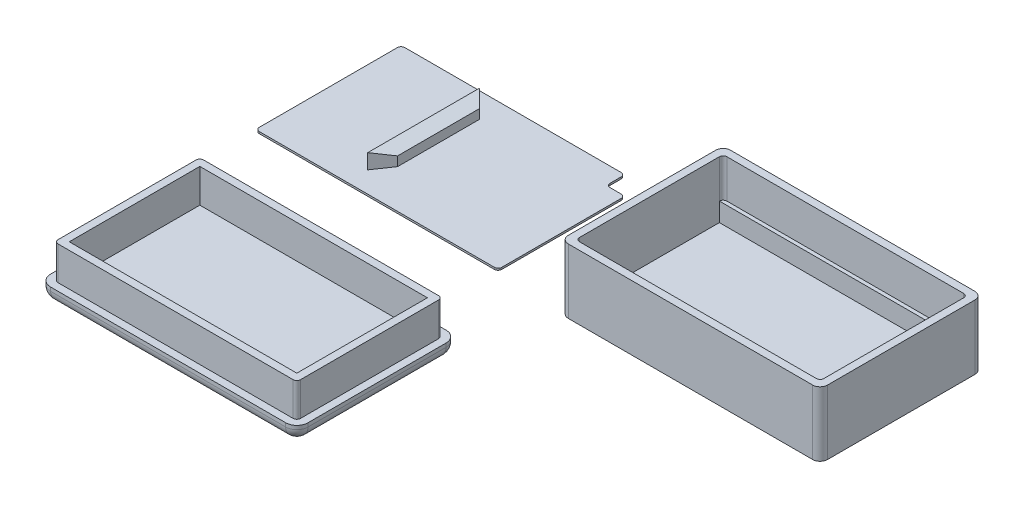
SolidWorks part; units mm, degrees
ref_plane "Front Plane" through (0, 0, 0) normal (0, 0, 1) x (1, 0, 0)
ref_plane "Top Plane" through (0, 0, 0) normal (0, 1, 0) x (1, 0, 0)
ref_plane "Right Plane" through (0, 0, 0) normal (1, 0, 0) x (0, 0, -1)
sketch "Sketch1" plane through (0, 0, 0) normal (0, 1, 0) x (1, 0, 0)
  line L0 (-58.3709, -20.404) -> (-58.3709, 18.596)
  line L1 (-58.3709, 18.596) -> (1.6291, 18.596)
  line L2 (1.6291, 18.596) -> (1.6291, 13.596)
  line L3 (1.6291, 13.596) -> (6.6291, 13.596)
  line L4 (6.6291, 13.596) -> (6.6291, -20.404)
  line L5 (6.6291, -20.404) -> (-58.3709, -20.404)
  dimension "D1" = 39
  dimension "D2" = 65
  dimension "D3" = 60
  dimension "D4" = 34
extrude "Boss-Extrude1" add sketch "Sketch1" along normal blind 0.5
fillet "Fillet2" radius 1 1 edges at (6.6291, 0.25, 20.404)
fillet "Fillet3" radius 1 3 edges at (1.6291, 0.25, -18.596) (1.6291, 0.25, -13.596) (6.6291, 0.25, -13.596)
fillet "Fillet4" radius 1 1 edges at (-58.3709, 0.25, -18.596)
fillet "Fillet5" radius 1 1 edges at (-58.3709, 0.25, 20.404)
sketch "Sketch3" plane through (0, 0, 0) normal (0, -1, 0) x (1, 0, 0)
  line L0 (92.1671, 19.6286) -> (27.1671, 19.6286) construction
  line L1 (92.4171, 19.8786) -> (26.9171, 19.8786)
  line L2 (92.4171, 19.8786) -> (92.4171, -19.6214)
  line L3 (92.4171, -19.6214) -> (26.9171, -19.6214)
  line L4 (26.9171, 19.8786) -> (26.9171, -19.6214)
  line L5 (27.1671, 19.6286) -> (27.1671, -19.3714) construction
  line L6 (92.1671, -19.3714) -> (27.1671, -19.3714) construction
  line L7 (92.1671, 19.6286) -> (92.1671, -19.3714) construction
  line L8 (94.4171, 21.8786) -> (94.4171, -21.6214)
  line L9 (94.4171, -21.6214) -> (24.9171, -21.6214)
  line L10 (24.9171, 21.8786) -> (24.9171, -21.6214)
  line L11 (94.4171, 21.8786) -> (24.9171, 21.8786)
  dimension "D1" = 65
  dimension "D2" = 39
  dimension "D4" = 2
  dimension "D3" = 0.25
extrude "Boss-Extrude2" add sketch "Sketch3" against normal blind 17.3 separate body
sketch "Sketch5" plane through (0, 0, 0) normal (0, -1, 0) x (1, 0, 0)
  line L5 (24.9171, -21.6214) -> (94.4171, -21.6214)
  line L6 (24.9171, -21.6214) -> (24.9171, 21.8786)
  line L7 (24.9171, 21.8786) -> (94.4171, 21.8786)
  line L8 (94.4171, -21.6214) -> (94.4171, 21.8786)
extrude "Boss-Extrude3" add sketch "Sketch5" against normal blind 2 contours L6 L5 L8 L7
fillet "Fillet6" radius 1 1 edges at (26.9171, 9.65, 19.8786)
fillet "Fillet7" radius 1 1 edges at (26.9171, 9.65, -19.6214)
fillet "Fillet8" radius 1 1 edges at (92.4171, 9.65, -19.6214)
fillet "Fillet9" radius 1 1 edges at (92.4171, 9.65, 19.8786)
sketch "Sketch7" plane through (-22.9055, 0.5, 42.5387) normal (0, 1, 0) x (1, 0, 0)
  line L0 (-36.3598, -30.9223) -> (-36.3598, 8.0777)
  line L1 (-36.3598, 8.0777) -> (23.6402, 8.0777)
  line L4 (28.6402, 3.0777) -> (28.6402, -30.9223)
  line L5 (28.6402, -30.9223) -> (-36.3598, -30.9223)
  line L8 (28.6402, 3.0777) -> (28.6402, 8.0777)
  line L9 (28.6402, 8.0777) -> (23.6402, 8.0777)
  dimension "D1" = 39
  dimension "D2" = 65
  dimension "D3" = 60
  dimension "D4" = 34
extrude "Boss-Extrude5" add sketch "Sketch7" against normal blind 9
fillet "Fillet12" radius 1 2 edges at (5.7348, -4, 73.461) (5.7348, -4, 34.461)
fillet "Fillet13" radius 1 2 edges at (-59.2652, -4, 34.461) (-59.2652, -4, 73.461)
sketch "Sketch8" plane through (0, -8.5, 0) normal (0, -1, 0) x (-1, 0, 0)
  line L8 (58.2652, -32.461) -> (-4.7348, -32.461)
  line L9 (61.2652, -72.461) -> (61.2652, -35.461)
  line L10 (-4.7348, -75.461) -> (58.2652, -75.461)
  line L11 (-7.7348, -35.461) -> (-7.7348, -72.461)
  line L12 (58.2652, -32.461) -> (-4.7348, -32.461)
  line L13 (61.2652, -72.461) -> (61.2652, -35.461)
  line L14 (-4.7348, -75.461) -> (58.2652, -75.461)
  line L15 (-7.7348, -35.461) -> (-7.7348, -72.461)
  arc A8 (61.2652, -35.461) -> (58.2652, -32.461) centre (58.2652, -35.461) ccw
  arc A9 (58.2652, -75.461) -> (61.2652, -72.461) centre (58.2652, -72.461) ccw
  arc A10 (-7.7348, -72.461) -> (-4.7348, -75.461) centre (-4.7348, -72.461) ccw
  arc A11 (-4.7348, -32.461) -> (-7.7348, -35.461) centre (-4.7348, -35.461) ccw
  arc A12 (61.2652, -35.461) -> (58.2652, -32.461) centre (58.2652, -35.461) ccw
  arc A13 (58.2652, -75.461) -> (61.2652, -72.461) centre (58.2652, -72.461) ccw
  arc A14 (-7.7348, -72.461) -> (-4.7348, -75.461) centre (-4.7348, -72.461) ccw
  arc A15 (-4.7348, -32.461) -> (-7.7348, -35.461) centre (-4.7348, -35.461) ccw
  dimension "D1" = 2
extrude "Boss-Extrude6" add sketch "Sketch8" along normal blind 4
sketch "Sketch9" plane through (0, 0.5, 0) normal (0, 1, 0) x (1, 0, 0)
  line L8 (3.7348, -36.461) -> (-57.2652, -36.461)
  line L9 (-57.2652, -36.461) -> (-57.2652, -71.461)
  line L10 (-57.2652, -71.461) -> (3.7348, -71.461)
  line L11 (3.7348, -71.461) -> (3.7348, -36.461)
  line L12 (3.7348, -36.461) -> (-57.2652, -36.461)
  line L13 (-57.2652, -36.461) -> (-57.2652, -71.461)
  line L14 (-57.2652, -71.461) -> (3.7348, -71.461)
  line L15 (3.7348, -71.461) -> (3.7348, -36.461)
  dimension "D1" = 2
extrude "Boss-Extrude7" add sketch "Sketch9" against normal up to surface (9 mm away) separate body up to face at (-26.7652, -8.5, 53.961)
combine bodies "Combine1" operation type subtract main body 106 bodies to subtract 107
fillet "Fillet15" radius 3 8 edges at (-61.2652, -12.5, 53.961) (-60.3866, -12.5, 74.5824) (-26.7652, -12.5, 75.461) (6.8561, -12.5, 74.5824) (7.7348, -12.5, 53.961) (6.8561, -12.5, 33.3397) (-26.7652, -12.5, 32.461) (-60.3866, -12.5, 33.3397)
sketch "Sketch19" plane through (0, 0, 0) normal (0, 0, 1) x (1, 0, 0)
  line L0 (-18.7232, 15.7306) -> (-18.7232, 19.7306)
  line L1 (-18.7232, 19.7306) -> (-14.7232, 19.7306) construction
  line L2 (-18.7232, 19.7306) -> (-14.7232, 18.9806)
  line L3 (-14.7232, 18.9806) -> (-14.7232, 16.4806)
  line L4 (-18.7232, 17.7306) -> (-14.7232, 17.7306) construction
  line L5 (-18.7232, 15.7306) -> (-14.7232, 16.4806)
  dimension "D1" = 2
  dimension "D2" = 4
  dimension "D3" = 2.5
extrude "Boss-Extrude8" add sketch "Sketch19" along normal blind 30 separate body
ref_plane "Plane1" through (0, 19.7306, 0) normal (0, 1, 0) x (-1, 0, 0)
sketch "Sketch20" plane through (0, 19.7306, 0) normal (0, 1, 0) x (-1, 0, 0)
  line L0 (18.7232, 30) -> (14.7232, 30)
  line L1 (14.7232, 30) -> (14.7232, 26)
  line L2 (18.7232, 15) -> (14.7232, 15) construction
  line L3 (14.7232, 30) -> (14.7232, 0) construction
  line L4 (14.7232, 26) -> (18.7232, 30)
  line L5 (18.7232, 30) -> (18.7232, 0) construction
  line L6 (14.7232, 0) -> (14.7232, 4)
  line L7 (18.7232, 0) -> (14.7232, 0)
  line L8 (14.7232, 4) -> (18.7232, 0)
  dimension "D1" = 4
extrude "Boss-Extrude9" add sketch "Sketch20" against normal up to surface (3.25 mm away) separate body up to face at (-16.7232, 16.1056, 15)
combine bodies "Combine2" operation type subtract main body 113 bodies to subtract 114 115
fillet "Fillet16" radius 2 4 edges at (94.4171, 8.65, -21.6214) (24.9171, 8.65, -21.6214) (24.9171, 8.65, 21.8786) (94.4171, 8.65, 21.8786)
sketch "Sketch21" plane through (0, 2, 0) normal (0, 1, 0) x (1, 0, 0)
  line L0 (26.9171, -0.1286) -> (92.4171, -0.1286) construction
  line L1 (27.1671, -18.6286) -> (87.1671, -18.6286) construction
  line L2 (27.1671, -18.6286) -> (27.1671, 18.3714) construction
  line L3 (27.1671, 18.3714) -> (87.1671, 18.3714) construction
  line L4 (87.1671, -18.6286) -> (87.1671, 18.3714) construction
  line L5 (26.9171, -18.8786) -> (26.9171, 18.6214) construction
  line L6 (92.4171, -18.8786) -> (92.4171, 18.6214) construction
  line L7 (26.9171, -18.8786) -> (26.9171, 18.6214)
  line L8 (26.9171, 18.6214) -> (87.4171, 18.6214)
  line L9 (87.4171, -18.8786) -> (87.4171, 18.6214)
  line L10 (26.9171, -18.8786) -> (87.4171, -18.8786)
  line L11 (27.9171, -19.8786) -> (91.4171, -19.8786)
  line L12 (92.4171, -18.8786) -> (92.4171, 18.6214)
  line L13 (91.4171, 19.6214) -> (27.9171, 19.6214)
  line L14 (26.9171, 18.6214) -> (26.9171, -18.8786)
  line L15 (27.9171, -19.8786) -> (91.4171, -19.8786)
  line L16 (92.4171, -18.8786) -> (92.4171, 18.6214)
  line L17 (91.4171, 19.6214) -> (27.9171, 19.6214)
  arc A4 (91.4171, -19.8786) -> (92.4171, -18.8786) centre (91.4171, -18.8786) ccw
  arc A5 (92.4171, 18.6214) -> (91.4171, 19.6214) centre (91.4171, 18.6214) ccw
  arc A6 (27.9171, 19.6214) -> (26.9171, 18.6214) centre (27.9171, 18.6214) ccw
  arc A7 (26.9171, -18.8786) -> (27.9171, -19.8786) centre (27.9171, -18.8786) ccw
  arc A8 (91.4171, -19.8786) -> (92.4171, -18.8786) centre (91.4171, -18.8786) ccw
  arc A9 (92.4171, 18.6214) -> (91.4171, 19.6214) centre (91.4171, 18.6214) ccw
  arc A10 (27.9171, 19.6214) -> (26.9171, 18.6214) centre (27.9171, 18.6214) ccw
  arc A11 (26.9171, -18.8786) -> (27.9171, -19.8786) centre (27.9171, -18.8786) ccw
  line M13 (27.9171, -19.8786) -> (91.4171, -19.8786)
  arc M14 (91.4171, -19.8786) -> (92.4171, -18.8786) centre (91.4171, -18.8786) ccw
  line M15 (92.4171, -18.8786) -> (92.4171, 18.6214)
  arc M16 (92.4171, 18.6214) -> (91.4171, 19.6214) centre (91.4171, 18.6214) ccw
  line M17 (91.4171, 19.6214) -> (27.9171, 19.6214)
  arc M18 (27.9171, 19.6214) -> (26.9171, 18.6214) centre (27.9171, 18.6214) ccw
  arc M20 (26.9171, -18.8786) -> (27.9171, -19.8786) centre (27.9171, -18.8786) ccw
  dimension "D1" = 60
  dimension "D2" = 37
  dimension "D3" = 0
extrude "Boss-Extrude10" add sketch "Sketch21" along normal blind 5 contours L10 L8 L9 M20 M13 M14 M15 M16 M17 M18 region at (57.1671, 2, 19.6435)
sketch "Sketch16" plane through (5.7348, 0, 0) normal (1, 0, 0) x (0, 0, -1)
  line L0 (-72.461, -8.5) -> (-35.461, 0.5) construction
